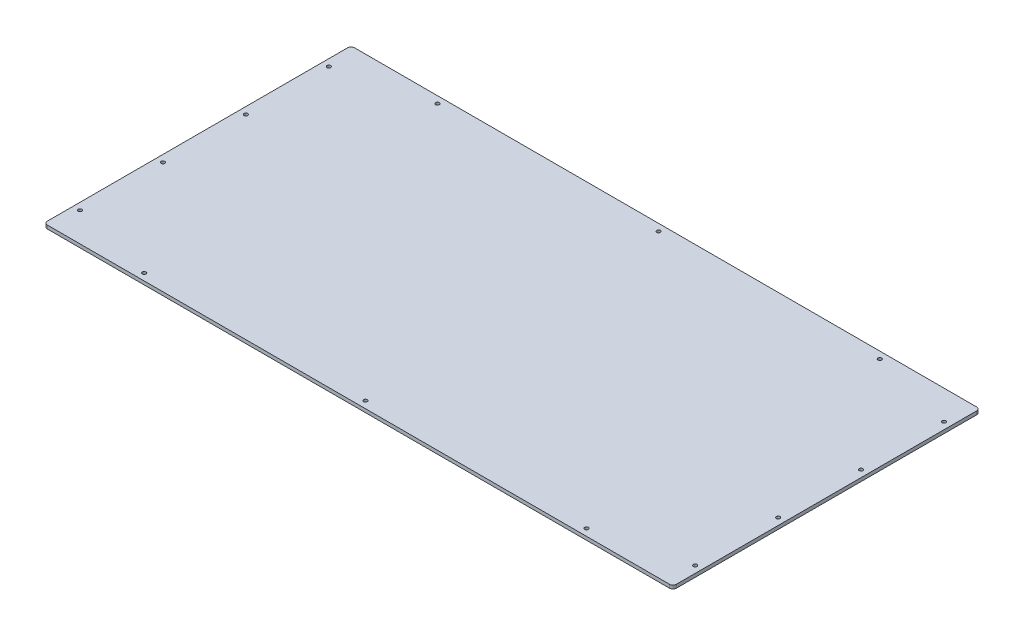
SolidWorks part; units mm, degrees
material "PE High Density"
ref_plane "Front Plane" through (0, 0, 0) normal (0, 0, 1) x (1, 0, 0)
ref_plane "Top Plane" through (0, 0, 0) normal (0, 1, 0) x (1, 0, 0)
ref_plane "Right Plane" through (0, 0, 0) normal (1, 0, 0) x (0, 0, -1)
sketch "Sketch1" plane through (0, 0, 0) normal (0, 1, 0) x (1, 0, 0)
  line L1 (-577.85, -282.133) -> (577.85, -282.133)
  line L2 (-577.85, -282.133) -> (-577.85, 282.133)
  line L3 (-577.85, 282.133) -> (577.85, 282.133)
  line L4 (577.85, -282.133) -> (577.85, 282.133)
  line L5 (-577.85, -282.133) -> (577.85, 282.133) construction
  line L6 (-577.85, 282.133) -> (577.85, -282.133) construction
  point P0 (0, 0)
  dimension "D1" = 564.2661
  dimension "D2" = 1155.7
extrude "Boss-Extrude1" add sketch "Sketch1" along normal blind 6.35
fillet "Fillet1" radius 6.35 4 edges at (577.85, 3.175, 282.133) (577.85, 3.175, -282.133) (-577.85, 3.175, 282.133) (-577.85, 3.175, -282.133)
sketch "Sketch2" plane through (0, 6.35, 0) normal (0, 1, 0) x (1, 0, 0)
  line L0 (-577.85, 275.783) -> (-577.85, -275.783) construction
  line L1 (571.5, 282.133) -> (-571.5, 282.133) construction
  line L2 (-571.5, -282.133) -> (571.5, -282.133) construction
  line L3 (577.85, -275.783) -> (577.85, 275.783) construction
  point P0 (-565.15, 228.6)
  point P1 (-565.15, 76.2)
  point P2 (-565.15, -76.2)
  point P3 (-565.15, -228.6)
  point P4 (565.15, 228.6)
  point P5 (565.15, 76.2)
  point P6 (565.15, -76.2)
  point P7 (565.15, -228.6)
  point P10 (-406.4, 269.433)
  point P11 (0, 269.433)
  point P12 (406.4, 269.433)
  point P13 (-406.4, -269.433)
  point P14 (0, -269.433)
  point P15 (406.4, -269.433)
  dimension "D1" = 152.4
  dimension "D2" = 152.4
  dimension "D3" = 12.7
  dimension "D6" = 12.7
  dimension "D4" = 152.4
  dimension "D5" = 76.2
  dimension "D7" = 12.7
  dimension "D8" = 12.7
  dimension "D9" = 406.4
  dimension "D10" = 406.4
hole_wizard "17/64 (0.26563) Diameter Hole1" positions "Sketch3" profile "Sketch5" hole size "17/64" standard "ANSI Inch" end condition through all
sketch "Sketch3" plane through (0, 6.35, 0) normal (0, 1, 0) x (1, 0, 0)
  point P0 (-565.15, 228.6)
  point P3 (-565.15, 76.2)
  point P6 (-565.15, -76.2)
  point P9 (-565.15, -228.6)
  point P12 (565.15, 228.6)
  point P15 (565.15, 76.2)
  point P18 (565.15, -76.2)
  point P21 (565.15, -228.6)
  point P24 (-406.4, 269.433)
  point P27 (0, 269.433)
  point P30 (406.4, 269.433)
  point P33 (406.4, -269.433)
  point P36 (0, -269.433)
  point P39 (-406.4, -269.433)
sketch "Sketch5" plane through (-565.15, 6.35, -228.6) normal (1, 0, 0) x (0, 0, 1)
  line L0 (0, 0) -> (0, 6.35)
  line L1 (0, 6.35) -> (3.3735, 6.35)
  line L2 (3.3735, 6.35) -> (3.3735, 0)
  line L5 (3.3735, 0) -> (0, 0)
  line L11 (0, -6.35) -> (0, 107.95) construction
  dimension "Thru Hole Dia." = 6.747
  dimension "Thru Hole Depth" = 6.35
equation "\"D5@Sketch2\"=\"D4@Sketch2\"/2"
